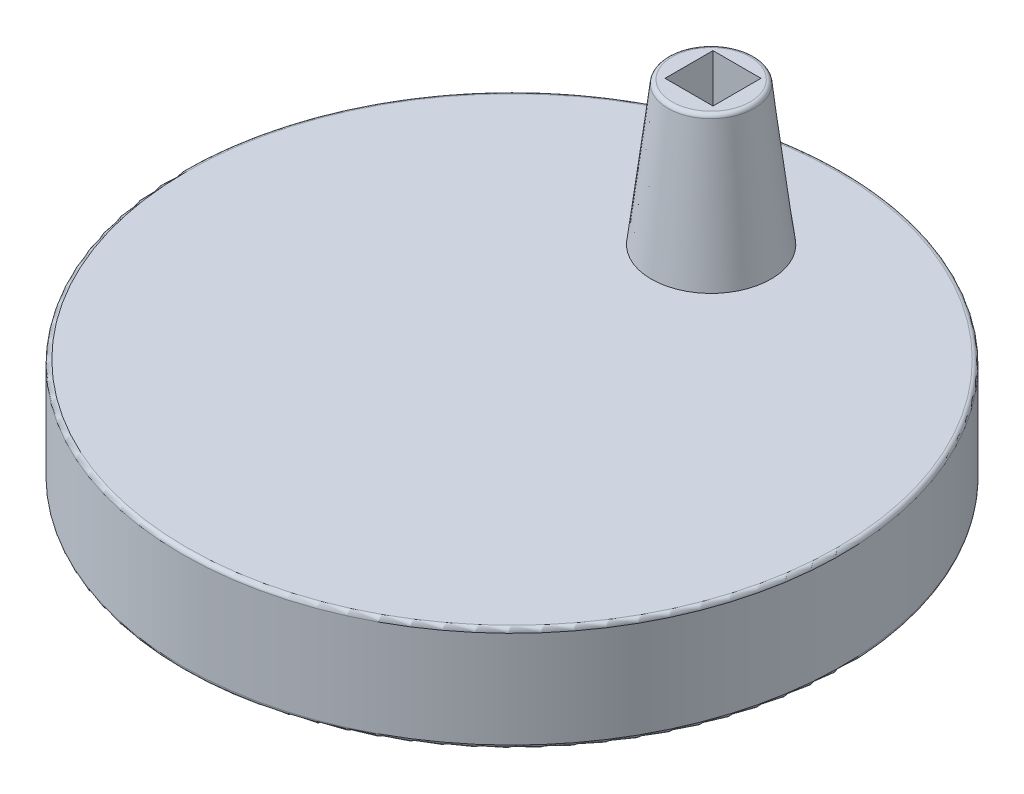
SolidWorks part; units mm, degrees
material "AISI 1020"
ref_plane "Front Plane" through (0, 0, 0) normal (0, 0, 1) x (1, 0, 0)
ref_plane "Top Plane" through (0, 0, 0) normal (0, 1, 0) x (1, 0, 0)
ref_plane "Right Plane" through (0, 0, 0) normal (1, 0, 0) x (0, 0, -1)
sketch "Sketch2" plane through (0, 0, 0) normal (0, 1, 0) x (1, 0, 0)
  line L0 (0, -80.35) -> (0, 33.95) construction
  circle A0 centre (0, 0) radius 80.35
  circle A1 centre (0, 48.55) radius 14.6
  dimension "D1" = 160.7
  dimension "D2" = 29.2
extrude "Boss-Extrude1" add sketch "Sketch2" against normal blind 25.6 contours A0
sketch "Sketch4" plane through (0, 0, 0) normal (0, 1, 0) x (1, 0, 0)
  line L0 (0, -80.35) -> (0, 33.95) construction
  circle A0 centre (0, 48.55) radius 14.6
  circle A2 centre (0, 0) radius 80.35 construction
  dimension "D2" = 29.2
  dimension "D1" = 114.3
ref_plane "Plane1" through (0, 34.88, 0) normal (0, 1, 0) x (1, 0, 0)
sketch "Sketch6" plane through (0, 34.88, 0) normal (0, 1, 0) x (1, 0, 0)
  circle A1 centre (0, 48.55) radius 10.4
  circle A3 centre (0, 0) radius 80.35 construction
  dimension "D3" = 20.8
  dimension "D1" = 48.55
loft "Loft1" add profiles "Sketch4", "Sketch6" connector at (0, 0, -33.95) connector at (0, 34.88, -38.15)
sketch "Sketch7" plane through (0, 34.88, 0) normal (0, 1, 0) x (1, 0, 0)
  line L0 (0, 38.6) -> (0, 49) construction
  line L2 (-5.85, 43.15) -> (5.85, 43.15)
  line L3 (-5.85, 43.15) -> (-5.85, 54.85)
  line L4 (-5.85, 54.85) -> (5.85, 54.85)
  line L5 (5.85, 43.15) -> (5.85, 54.85)
  line L6 (-5.85, 43.15) -> (5.85, 54.85) construction
  line L7 (-3.9158, 52.9158) -> (5.85, 43.15) construction
  dimension "D1" = 10.4
  dimension "D2" = 5.85
  dimension "D3" = 11.7
  dimension "D4" = 11.7
extrude "Cut-Extrude1" cut sketch "Sketch7" against normal blind 25.6
fillet "Fillet1" radius 1 1 edges at (0, 34.88, -38.15)
fillet "Fillet2" radius 1 2 edges at (0, -25.6, 80.35) (0, 0, 80.35)
sketch "Sketch15" plane through (0, 0, -54.85) normal (0, 0, 1) x (1, 0, 0)
  line L0 (0, 0) -> (0, 24)
  circle A0 centre (0, 24) radius 1.75
  dimension "D2" = 3.5
  dimension "D1" = 24
extrude "Cut-Extrude3" cut sketch "Sketch15" against normal through all contours A0 region at (1.2024, 22.7976, -54.85)
thread "Thread2" pitch 0.5 method extrude profile "Thread Profile3" start angle 0, offset 0, length 5.5, pitch 0.5, diameter 3.5
ref_plane "Plane5" through (-1.75, 24, -54.85) normal (0, -1, 0) x (-1, 0, 0)
sketch "Thread Profile3" plane through (-1.75, 24, -54.85) normal (0, -1, 0) x (-1, 0, 0)
  line L0 (0, 0) -> (0, 0.5) construction
  line L11 (0, 0) -> (0, 0.4375)
  line L12 (0, 0.4375) -> (-0.2706, 0.2812)
  line L13 (-0.2706, 0.2812) -> (-0.2706, 0.1562)
  line L15 (-0.2706, 0.1562) -> (0, 0)
  line L17 (-0.2706, 0.2187) -> (0, 0.2187) construction
  point P2 (0, 0)
  dimension "Pitch" = 0.5
  dimension "Profile_Angle" = 60
  dimension "Profile_Land" = 0.125
  dimension "Profile_Height" = 0.2706
